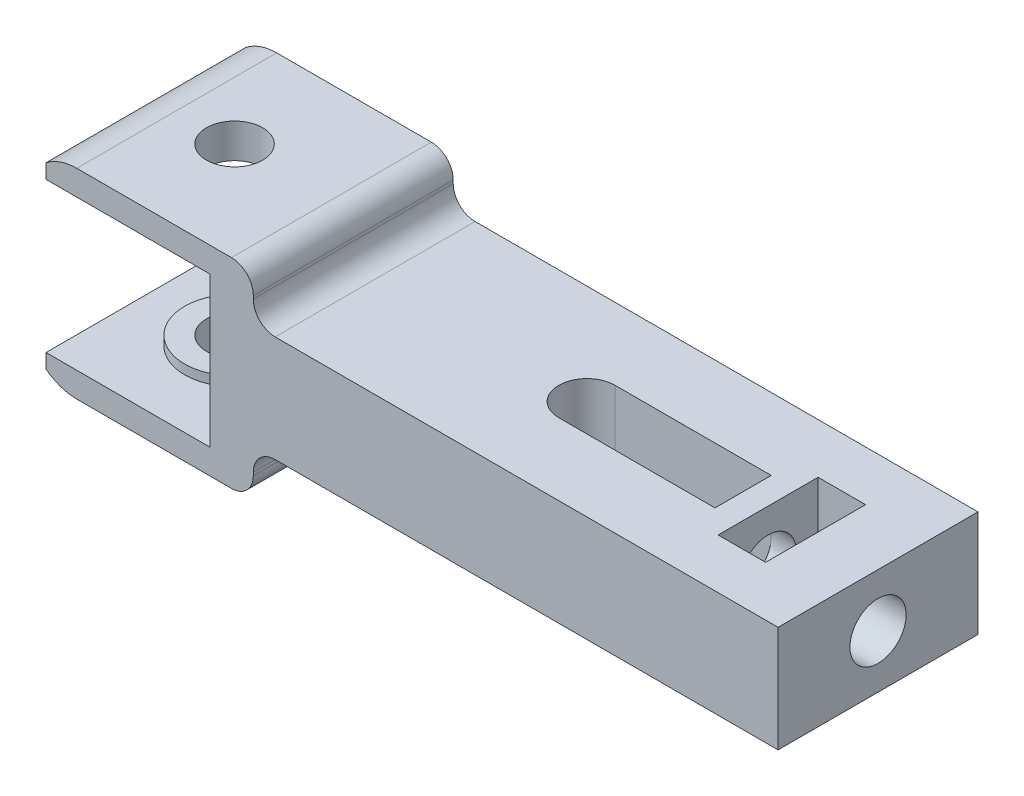
SolidWorks part; units mm, degrees
ref_plane "Front Plane" through (0, 0, 0) normal (0, 0, 1) x (1, 0, 0)
ref_plane "Top Plane" through (0, 0, 0) normal (0, 1, 0) x (1, 0, 0)
ref_plane "Right Plane" through (0, 0, 0) normal (1, 0, 0) x (0, 0, -1)
sketch "Sketch1" plane through (0, 0, 0) normal (0, 0, 1) x (1, 0, 0)
  line L0 (0, 0) -> (-42, 0)
  line L1 (-42, 0) -> (-42, 3.75)
  line L2 (-42, 3.75) -> (-60, 3.75)
  line L3 (-60, 3.75) -> (-60, 0.75)
  line L4 (-60, 0.75) -> (-46, 0.75)
  line L5 (-46, 0.75) -> (-46, -9.25)
  line L6 (0, 0) -> (0, -8.5)
  line L7 (0, -4.25) -> (-46, -4.25) construction
  line L8 (-60, -9.25) -> (-46, -9.25)
  line L9 (-60, -12.25) -> (-60, -9.25)
  line L10 (-42, -12.25) -> (-60, -12.25)
  line L11 (-42, -8.5) -> (-42, -12.25)
  line L12 (0, -8.5) -> (-42, -8.5)
  dimension "D1" = 60
  dimension "D2" = 14
  dimension "D3" = 4.25
  dimension "D4" = 5
  dimension "D5" = 3
  dimension "D6" = 18
extrude "Boss-Extrude1" add sketch "Sketch1" along normal blind 16
sketch "Sketch2" plane through (0, 0, 0) normal (0, 1, 0) x (1, 0, 0)
  line L0 (0, -8) -> (-42, -8) construction
  line L1 (0, -16) -> (0, 0) construction
  line L2 (-42, -16) -> (-42, 0) construction
  line L4 (-8.8, -4) -> (-5, -4)
  line L5 (-8.8, -4) -> (-8.8, -12)
  line L6 (-8.8, -12) -> (-5, -12)
  line L7 (-5, -4) -> (-5, -12)
  line L8 (-8.8, -4) -> (-5, -12) construction
  line L9 (-8.8, -12) -> (-5, -4) construction
  line L10 (-23.3, -10.25) -> (-10.8, -10.25)
  line L12 (-23.3, -5.75) -> (-10.8, -5.75)
  line L13 (-10.8, -10.25) -> (-10.8, -5.75)
  line L14 (-23.3, -10.25) -> (-10.8, -5.75) construction
  line L15 (-23.3, -5.75) -> (-10.8, -10.25) construction
  arc A0 (-23.3, -5.75) -> (-23.3, -10.25) centre (-23.3, -8) ccw
  point P6 (-6.9, -8)
  point P11 (-17.05, -8)
  dimension "D7" = 2.25
  dimension "D1" = 8
  dimension "D2" = 3.8
  dimension "D3" = 5
  dimension "D4" = 2
  dimension "D5" = 4.5
  dimension "D6" = 12.5
extrude "Cut-Extrude1" cut sketch "Sketch2" against normal through all
sketch "Sketch3" plane through (0, 0, 0) normal (1, 0, 0) x (0, 0, -1)
  line L0 (-8, 0) -> (-8, -8.5) construction
  line L1 (-16, 0) -> (0, 0) construction
  line L2 (-16, -8.5) -> (0, -8.5) construction
  circle A0 centre (-8, -4.25) radius 2.25
  dimension "D1" = 4.5
extrude "Cut-Extrude2" cut sketch "Sketch3" against normal up to surface (10.8 mm away) up to face at (-10.8, -4.25, 8)
fillet "Fillet1" radius 1.75 4 edges at (-42, -8.5, 8) (-42, 3.75, 8) (-42, 0, 8) (-42, -12.25, 8)
sketch "Sketch4" plane through (0, -9.25, 0) normal (0, 1, 0) x (1, 0, 0)
  line L0 (-60, -8) -> (-43.75, -8) construction
  line L1 (-60, -16) -> (-60, 0) construction
  line L2 (-43.75, 0) -> (-43.75, -16) construction
  circle A0 centre (-51.875, -8) radius 9.25
  dimension "D1" = 18.5
extrude "Cut-Extrude3" cut sketch "Sketch4" along normal up to surface (10 mm away) up to face at (-53, 0.75, 8)
sketch "Sketch5" plane through (0, 3.75, 0) normal (0, 1, 0) x (1, 0, 0)
  line L0 (-60, -8) -> (-43.75, -8) construction
  line L1 (-60, -16) -> (-60, 0) construction
  line L2 (-43.75, -16) -> (-43.75, 0) construction
  circle A0 centre (-51.5, -8) radius 2.25
  dimension "D1" = 4.5
  dimension "D2" = 8.5
extrude "Cut-Extrude4" cut sketch "Sketch5" against normal through all
fillet "Fillet2" radius 4 2 edges at (-60, -12.25, 8) (-60, 3.75, 8)
sketch "Sketch6" plane through (0, -9.25, 0) normal (0, 1, 0) x (1, 0, 0)
  line L0 (-51.875, 1.25) -> (-60, 1.25)
  line L1 (-60, -16) -> (-60, 0) construction
  line L2 (-51.875, -17.25) -> (-60, -17.25)
  line L3 (-60, -17.25) -> (-60, 1.25)
  arc A0 (-51.875, -17.25) -> (-51.875, 1.25) centre (-51.875, -8) ccw
  arc A1 (-46, -15.1447) -> (-46, -0.8553) centre (-51.875, -8) ccw construction
extrude "Cut-Extrude5" cut sketch "Sketch6" against normal blind 1
sketch "Sketch7" plane through (0, -10.25, 0) normal (0, 1, 0) x (1, 0, 0)
  circle A0 centre (-51.5, -8) radius 4
  circle A1 centre (-51.5, -8) radius 2.25
  circle A2 centre (-51.5, -8) radius 2.25 construction
  dimension "D1" = 8
extrude "Boss-Extrude2" add sketch "Sketch7" along normal blind 0.75
ref_plane "Plane1" through (0, -4.25, 0) normal (0, 1, 0) x (1, 0, 0)
mirror "Mirror1" about plane through (0, -4.25, 0) normal (0, 1, 0) of "Boss-Extrude2", "Cut-Extrude5"
sketch "Sketch8" plane through (0, 0, 16) normal (0, 0, 1) x (1, 0, 0)
  line L0 (0, -4.25) -> (-60.5911, -4.25) construction
  line L1 (0, -8.5) -> (0, 0) construction
  line L2 (8.8, -4.25) -> (-8.8, -4.25) construction
  line L3 (-43.75, 3.75) -> (-56.127, 3.75) construction
  line L4 (-62.5911, -12.25) -> (-58.5911, -12.25)
  line L5 (-62.5911, -12.25) -> (-62.5911, 3.75)
  line L6 (-62.5911, 3.75) -> (-58.5911, 3.75)
  line L7 (-58.5911, -12.25) -> (-58.5911, 3.75)
  line L8 (-62.5911, -12.25) -> (-58.5911, 3.75) construction
  line L9 (-62.5911, 3.75) -> (-58.5911, -12.25) construction
  dimension "D1" = 1
  dimension "D2" = 2
extrude "Cut-Extrude6" cut sketch "Sketch8" against normal through all
sketch "Sketch9" plane through (0, 0, 16) normal (0, 0, 1) x (1, 0, 0)
  line L0 (-58.5911, -10.25) -> (-47.2315, -10.25) construction
  line L1 (-47.2315, 1.75) -> (-45.4815, 1.75)
  line L2 (-47.2315, 1.75) -> (-47.2315, -10.25)
  line L3 (-47.2315, -10.25) -> (-45.4815, -10.25)
  line L4 (-45.4815, 1.75) -> (-45.4815, -10.25)
  dimension "D1" = 1.75
extrude "Cut-Extrude7" cut sketch "Sketch9" against normal through all
equation "\"X-ROD-SPACING\"=45"
equation "\"Y-ROD-SPACING\"=75"
equation "\"Z-ROD-SPACING\"=17.5"
equation "\"Y-BED-OFFSET\"=2"
equation "\"Y-BED-ROD-INSET\"=3.5"
equation "\"T-SLOT-NUT-FILLET-RADIUS\"=0.5"
equation "\"T-SLOT-SCREW-SHAFT-RADIUS\"=1.55"
equation "\"T-SLOT-SCREW-SHAFT-CUTOUT-LENGTH\"=11"
equation "\"T-SLOT-NUT-DEPTH\"=3.5"
equation "\"T-SLOT-NUT-WIDTH\"=2.85"
equation "\"T-SLOT-NUT-END-DISTANCE\"=8"
equation "\"ACRYLIC-THICKNESS\"=10"
equation "\"ACRYLIC-TAB-CUTOUT-SIZE\"=\"ACRYLIC-THICKNESS\"+\"ACRYLIC-TAB-TOLERANCE\"*2"
equation "\"ACRYLIC-TAB-WIDTH\"=\"ACRYLIC-THICKNESS\""
equation "\"ACRYLIC-M3-HOLE\"=2.9"
equation "\"SMOOTHROD-CAP-SCREW-DISTANCE\"=20"
equation "\"FRAME-WIDTH-INNER\"=370"
equation "\"NEMA17-HOLE-SPACING\"=31"
equation "\"NEMA17-CENTRAL-CUTOUT\"=22.5"
equation "\"Z-BRACKET-REACH\"=57"
equation "\"TOP-BRACKET-SPACING\"=40"
equation "\"SMOOTHROD-X-LENGTH\"=350"
equation "\"SMOOTHROD-Y-LENGTH\"=350"
equation "\"SMOOTHROD-Z-LENGTH\"=350"
equation "\"SMOOTHROD-TIGHTENING-HEADROOM\"=.25"
equation "\"LEADSCREW-Z-LENGTH\"=300"
equation "\"SCREW-HEAD-RADIUS\"=6"
equation "\"PRINTED-X-SMOOTHROD-DIAMETER\"=8.8"
equation "\"PRINTED-X-SMOOTHROD-CUTOUT\"=10"
equation "\"PRINTED-X-BASE-HEIGHT\"=10"
equation "\"PRINTED-LM8UU-CUTOUT-SIZE\"=15.5"
equation "\"PRINTED-LM8UU-CUTOUT-LENGTH\"=24.5"
equation "\"PRINTED-X-IDLER-HEIGHT\"=16"
equation "\"D1@Boss-Extrude1\"=\"PRINTED-X-IDLER-HEIGHT\""
